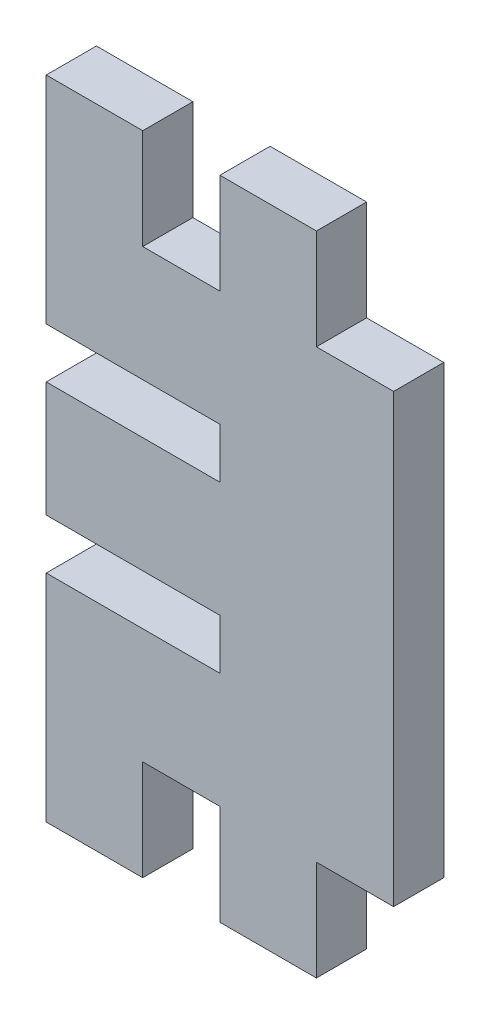
SolidWorks part; units mm, degrees
ref_plane "Front Plane" through (0, 0, 0) normal (0, 0, 1) x (1, 0, 0)
ref_plane "Top Plane" through (0, 0, 0) normal (0, 1, 0) x (1, 0, 0)
ref_plane "Right Plane" through (0, 0, 0) normal (1, 0, 0) x (0, 0, -1)
sketch "Sketch1" plane through (0, 0, 0) normal (0, 0, 1) x (1, 0, 0)
  line L0 (0, 0) -> (60.2571, 0) construction
  line L1 (55, 0) -> (-55, 0) construction
  line L2 (-18, -5.975) -> (-18, 5.975)
  line L3 (-18, 5.975) -> (0, 5.975)
  line L4 (0, 5.975) -> (0, 11.175)
  line L5 (0, 11.175) -> (-18, 11.175)
  line L6 (-18, 11.175) -> (-18, 33.525)
  line L7 (0, -55) -> (0, 55) construction
  line L8 (0, 1.5761) -> (0, 45.6913) construction
  line L9 (-18, 33.525) -> (-8, 33.525)
  line L10 (0, 33.525) -> (0, 23.125)
  line L11 (0, 23.125) -> (-8, 23.125)
  line L12 (-8, 23.125) -> (-8, 33.525)
  line L13 (0, 33.525) -> (10, 33.525)
  line L14 (10, 33.525) -> (10, 23.125)
  line L15 (10, 23.125) -> (18, 23.125)
  line L16 (18, 23.125) -> (18, -23.125)
  line L17 (-18, -5.975) -> (0, -5.975)
  line L18 (0, -5.975) -> (0, -11.175)
  line L19 (0, -11.175) -> (-18, -11.175)
  line L20 (-18, -11.175) -> (-18, -33.525)
  line L21 (0, -33.525) -> (0, -23.125)
  line L22 (-18, -33.525) -> (-8, -33.525)
  line L23 (10, -23.125) -> (18, -23.125)
  line L24 (10, -33.525) -> (10, -23.125)
  line L25 (0, -33.525) -> (10, -33.525)
  line L26 (-8, -23.125) -> (-8, -33.525)
  line L27 (0, -23.125) -> (-8, -23.125)
  line L28 (43.6365, 23.125) -> (43.537, 23.125)
  line L29 (0, -23.125) -> (0, -11.175) construction
  line L30 (0, -11.175) -> (-0.0397, -11.1768)
  point P23 (-18, 0)
  point P30 (18, 0)
  dimension "D1" = 36
  dimension "D2" = 5.2
  dimension "D3" = 10.4
  dimension "D4" = 11.95
  dimension "D5" = 10
  dimension "D6" = 11.95
  dimension "D7" = 8
extrude "Boss-Extrude2" add sketch "Sketch1" along normal blind 5.2 contours L27 L21 L25 L24 L23 L16 L15 L14 L13 L10 L11 L12 L9 L6 L5 L4 L3 L2 L17 L18 L19 L20 L22 L26 region at (0.011, 0, 0)
